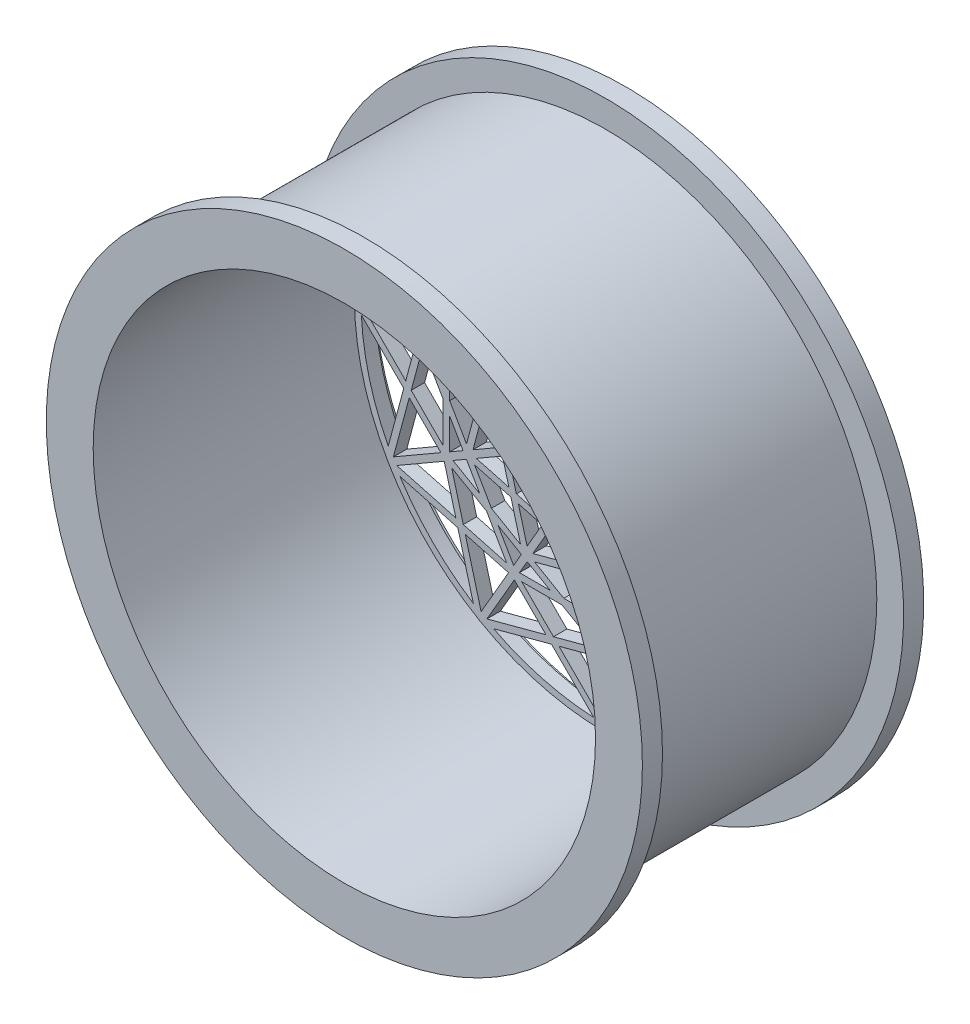
SolidWorks part; units mm, degrees
ref_plane "Front Plane" through (0, 0, 0) normal (0, 0, 1) x (1, 0, 0)
ref_plane "Top Plane" through (0, 0, 0) normal (0, 1, 0) x (1, 0, 0)
ref_plane "Right Plane" through (0, 0, 0) normal (1, 0, 0) x (0, 0, -1)
sketch "Sketch1" plane through (0, 0, 0) normal (0, 0, 1) x (1, 0, 0)
  circle A0 centre (0, 0) radius 40.5
  circle A1 centre (0, 0) radius 37.5
  dimension "D1" = 81
  dimension "D2" = 3
extrude "Boss-Extrude1" add sketch "Sketch1" along normal blind 36 contours A0 A1 region at (-39.3545, 0, 0)
sketch "Sketch2" plane through (0, 0, 0) normal (0, 0, -1) x (-1, 0, 0)
  circle A0 centre (0, 0) radius 40.5
  circle A1 centre (0, 0) radius 44.5
  circle A2 centre (0, 0) radius 40.5 construction
  circle M3 centre (0, 0) radius 37.5
  circle M4 centre (0, 0) radius 40.5
  dimension "D1" = 89
extrude "Boss-Extrude2" add sketch "Sketch2" along normal blind 3 contours A1 M4 | M3 | M4 M3 region at (39.3545, 0, 0) region at (43.2413, 0, 0) region at (0, 0, 0)
sketch "Sketch3" plane through (0, 0, 36) normal (0, 0, 1) x (1, 0, 0)
  circle A0 centre (0, 0) radius 37.5
  circle A1 centre (0, 0) radius 44.5
  circle A2 centre (0, 0) radius 37.5 construction
  dimension "D1" = 89
extrude "Boss-Extrude3" add sketch "Sketch3" along normal blind 3
sketch "Sketch4" plane through (0, 0, -3) normal (0, 0, -1) x (-1, 0, 0)
  circle A0 centre (0, 0) radius 5
  dimension "D1" = 10
extrude "Cut-Extrude1" cut sketch "Sketch4" against normal up to surface (3 mm away) up to face at (37.5, 0, 0)
sketch "Sketch5" plane through (0, 0, -3) normal (0, 0, -1) x (-1, 0, 0)
  circle A0 centre (0, 0) radius 37.5
  dimension "D1" = 75
extrude "Cut-Extrude2" cut sketch "Sketch5" against normal blind 1
sketch "Sketch6" plane through (0, 0, -2) normal (0, 0, -1) x (-1, 0, 0)
  line L0 (0, 0) -> (0, 37.5)
  line L1 (0, 0) -> (18.75, 32.476)
  line L2 (0, 0) -> (-18.75, 32.476)
  line L3 (-18.75, 32.476) -> (0, 27.4519)
  line L4 (0, 27.4519) -> (-11.887, 20.5889)
  line L5 (-11.887, 20.5889) -> (0, 17.4038)
  line L6 (0, 17.4038) -> (-7.5361, 13.0529)
  line L7 (-7.5361, 13.0529) -> (0, 11.0336)
  line L8 (0, 37.5) -> (-13.726, 23.774)
  line L9 (-13.726, 23.774) -> (0, 23.774)
  line L10 (0, 23.774) -> (-8.7019, 15.0721)
  line L11 (-8.7019, 15.0721) -> (0, 15.0721)
  line L12 (0, 15.0721) -> (-5.5168, 9.5554)
  line L13 (-16.7143, 32.4481) -> (-8.0741, 30.133)
  line L14 (-8.0741, 30.133) -> (-1.749, 36.4581)
  line L15 (-17.7134, 31.6806) -> (-13.6187, 24.5884)
  line L16 (-13.6187, 24.5884) -> (-8.8906, 29.3165)
  line L17 (-8.8906, 29.3165) -> (-17.7134, 31.6806)
  line L18 (-6.9588, 29.8341) -> (-0.5, 28.1035)
  line L19 (-0.5, 28.1035) -> (-0.5, 36.2929)
  line L20 (-0.5, 36.2929) -> (-6.9588, 29.8341)
  line L21 (-12.5188, 24.274) -> (-7.7753, 29.0176)
  line L22 (-7.7753, 29.0176) -> (-1.2954, 27.2814)
  line L23 (-1.2954, 27.2814) -> (-6.5042, 24.274)
  line L24 (-6.5042, 24.274) -> (-12.5188, 24.274)
  line L25 (-12.8599, 23.274) -> (-11.704, 21.2719)
  line L26 (-11.704, 21.2719) -> (-8.2363, 23.274)
  line L27 (-8.2363, 23.274) -> (-12.8599, 23.274)
  line L28 (-0.5, 26.5859) -> (-4.5042, 24.274)
  line L29 (-4.5042, 24.274) -> (-0.5, 24.274)
  line L30 (-0.5, 24.274) -> (-0.5, 26.5859)
  line L31 (-10.5916, 20.7595) -> (-6.2363, 23.274)
  line L32 (-6.2363, 23.274) -> (-1.2071, 23.274)
  line L33 (-1.2071, 23.274) -> (-5.1735, 19.3077)
  line L34 (-5.1735, 19.3077) -> (-10.5916, 20.7595)
  line L35 (-10.8505, 19.7935) -> (-8.5947, 15.8865)
  line L36 (-8.5947, 15.8865) -> (-5.99, 18.4912)
  line L37 (-5.99, 18.4912) -> (-10.8505, 19.7935)
  line L38 (-4.0581, 19.0088) -> (-0.5, 18.0554)
  line L39 (-0.5, 18.0554) -> (-0.5, 22.5669)
  line L40 (-0.5, 22.5669) -> (-4.0581, 19.0088)
  line L41 (-4.8746, 18.1923) -> (-7.4948, 15.5721)
  line L42 (-7.4948, 15.5721) -> (-4.1725, 15.5721)
  line L43 (-4.1725, 15.5721) -> (-1.2954, 17.2333)
  line L44 (-1.2954, 17.2333) -> (-4.8746, 18.1923)
  line L45 (-7.8359, 14.5721) -> (-7.3531, 13.7359)
  line L46 (-7.3531, 13.7359) -> (-5.9046, 14.5721)
  line L47 (-5.9046, 14.5721) -> (-7.8359, 14.5721)
  line L48 (-6.2407, 13.2234) -> (-3.3345, 12.4447)
  line L49 (-3.3345, 12.4447) -> (-1.2071, 14.5721)
  line L50 (-1.2071, 14.5721) -> (-3.9046, 14.5721)
  line L51 (-3.9046, 14.5721) -> (-6.2407, 13.2234)
  line L52 (-0.5, 16.5378) -> (-0.5, 15.5721)
  line L53 (-0.5, 15.5721) -> (-2.1725, 15.5721)
  line L54 (-2.1725, 15.5721) -> (-0.5, 16.5378)
  line L55 (-0.5, 13.865) -> (-2.2192, 12.1458)
  line L56 (-2.2192, 12.1458) -> (-0.5, 11.6852)
  line L57 (-0.5, 11.6852) -> (-0.5, 13.865)
  line L58 (-3.0357, 11.3293) -> (-4.1973, 10.1677)
  line L59 (-3.0357, 11.3293) -> (-1.4489, 10.9042)
  line L60 (-6.4995, 12.2575) -> (-5.4096, 10.3697)
  line L61 (-5.4096, 10.3697) -> (-4.151, 11.6282)
  line L62 (-4.151, 11.6282) -> (-6.4995, 12.2575)
  circle A0 centre (0, 0) radius 37.5 construction
  circle A1 centre (0, 0) radius 11
  circle A2 centre (0, 0) radius 5 construction
  circle A3 centre (0, 0) radius 36.5
  point P73 (0, 0)
  dimension "D1" = 30
  dimension "D2" = 6
  dimension "D3" = 45
  dimension "D4" = 45
  dimension "D5" = 1
  dimension "D6" = 0.5
  dimension "D7" = 0.5
  dimension "D8" = 0.5
  dimension "D9" = 0.5
  dimension "D10" = 0.5
  dimension "D11" = 0.5
  dimension "D12" = 0.5
  dimension "D13" = 0.5
  dimension "D14" = 0.5
  dimension "D15" = 0.5
  dimension "D16" = 0.5
  dimension "D17" = 0.5
  dimension "D18" = 0.5
  dimension "D19" = 0.5
  dimension "D20" = 0.5
  dimension "D21" = 0.5
  dimension "D22" = 0.5
  dimension "D23" = 0.5
  dimension "D24" = 0.5
  dimension "D25" = 0.5
  dimension "D26" = 0.5
  dimension "D27" = 0.5
  dimension "D28" = 0.5
  dimension "D29" = 0.5
  dimension "D30" = 0.5
  dimension "D31" = 0.5
  dimension "D32" = 0.5
  dimension "D33" = 0.5
  dimension "D34" = 0.5
  dimension "D35" = 0.5
  dimension "D36" = 0.5
  dimension "D37" = 0.5
  dimension "D38" = 0.5
  dimension "D39" = 0.5
  dimension "D40" = 0.5
  dimension "D41" = 0.5
  dimension "D42" = 0.5
  dimension "D43" = 0.5
  dimension "D44" = 0.5
  dimension "D45" = 0.5
  dimension "D46" = 0.5
  dimension "D47" = 0.5
  dimension "D48" = 0.5
  dimension "D49" = 0.5
  dimension "D50" = 0.5
  dimension "D51" = 0.5
  dimension "D52" = 0.5
  dimension "D53" = 0.5
extrude "Cut-Extrude3" cut sketch "Sketch6" against normal up to surface (2 mm away) contours L14 A3 L13 | L16 L17 L15 | L19 L20 L18 | L24 L23 L22 L21 | L29 L30 L28 | L26 L27 L25 | L34 L33 L32 L31 | L36 L37 L35 | L39 L40 L38 | L43 L44 L41 L42 | L50 L51 L48 L49 | L56 L57 L55 | L61 L62 L60 | A1 L59 L58 region at (2.9048, 10.8408, -2) region at (8.9398, 33.3637, -2) region at (13.4076, 28.5285, -2) region at (2.6529, 31.4102, -2) region at (7.0622, 26.3565, -2) region at (10.9334, 22.6067, -2) region at (1.8347, 25.0447, -2) region at (5.7697, 21.5328, -2) region at (8.4784, 18.0571, -2) region at (1.686, 19.8771, -2) region at (4.4808, 16.7224, -2) region at (3.6543, 13.6382, -2) region at (1.0731, 12.5654, -2) region at (5.3534, 11.4184, -2) up to face at (-5, 0, 0)
pattern_circular "CirPattern1" count 12 every 30 about axis through (0, 0, -2) along (0, 0, 1) of "Cut-Extrude3"
equation "\"spokewidth\"=0.5"
equation "\"D6@Sketch6\"=\"spokewidth\""
equation "\"D7@Sketch6\"=\"spokewidth\""
equation "\"D8@Sketch6\"=\"spokewidth\""
equation "\"D9@Sketch6\"=\"spokewidth\""
equation "\"D10@Sketch6\"=\"spokewidth\""
equation "\"D11@Sketch6\"=\"spokewidth\""
equation "\"D12@Sketch6\"=\"spokewidth\""
equation "\"D13@Sketch6\"=\"spokewidth\""
equation "\"D14@Sketch6\"=\"spokewidth\""
equation "\"D15@Sketch6\"=\"spokewidth\""
equation "\"D16@Sketch6\"=\"spokewidth\""
equation "\"D17@Sketch6\"=\"spokewidth\""
equation "\"D18@Sketch6\"=\"spokewidth\""
equation "\"D19@Sketch6\"=\"spokewidth\""
equation "\"D20@Sketch6\"=\"spokewidth\""
equation "\"D21@Sketch6\"=\"spokewidth\""
equation "\"D22@Sketch6\"=\"spokewidth\""
equation "\"D23@Sketch6\"=\"spokewidth\""
equation "\"D24@Sketch6\"=\"spokewidth\""
equation "\"D25@Sketch6\"=\"spokewidth\""
equation "\"D26@Sketch6\"=\"spokewidth\""
equation "\"D27@Sketch6\"=\"spokewidth\""
equation "\"D28@Sketch6\"=\"spokewidth\""
equation "\"D29@Sketch6\"=\"spokewidth\""
equation "\"D30@Sketch6\"=\"spokewidth\""
equation "\"D31@Sketch6\"=\"spokewidth\""
equation "\"D32@Sketch6\"=\"spokewidth\""
equation "\"D33@Sketch6\"=\"spokewidth\""
equation "\"D34@Sketch6\"=\"spokewidth\""
equation "\"D35@Sketch6\"=\"spokewidth\""
equation "\"D36@Sketch6\"=\"spokewidth\""
equation "\"D37@Sketch6\"=\"spokewidth\""
equation "\"D38@Sketch6\"=\"spokewidth\""
equation "\"D39@Sketch6\"=\"spokewidth\""
equation "\"D40@Sketch6\"=\"spokewidth\""
equation "\"D41@Sketch6\"=\"spokewidth\""
equation "\"D42@Sketch6\"=\"spokewidth\""
equation "\"D43@Sketch6\"=\"spokewidth\""
equation "\"D44@Sketch6\"=\"spokewidth\""
equation "\"D45@Sketch6\"=\"spokewidth\""
equation "\"D46@Sketch6\"=\"spokewidth\""
equation "\"D47@Sketch6\"=\"spokewidth\""
equation "\"D48@Sketch6\"=\"spokewidth\""
equation "\"D49@Sketch6\"=\"spokewidth\""
equation "\"D50@Sketch6\"=\"spokewidth\""
equation "\"D51@Sketch6\"=\"spokewidth\""
equation "\"D52@Sketch6\"=\"spokewidth\""
equation "\"D53@Sketch6\"=\"spokewidth\""
